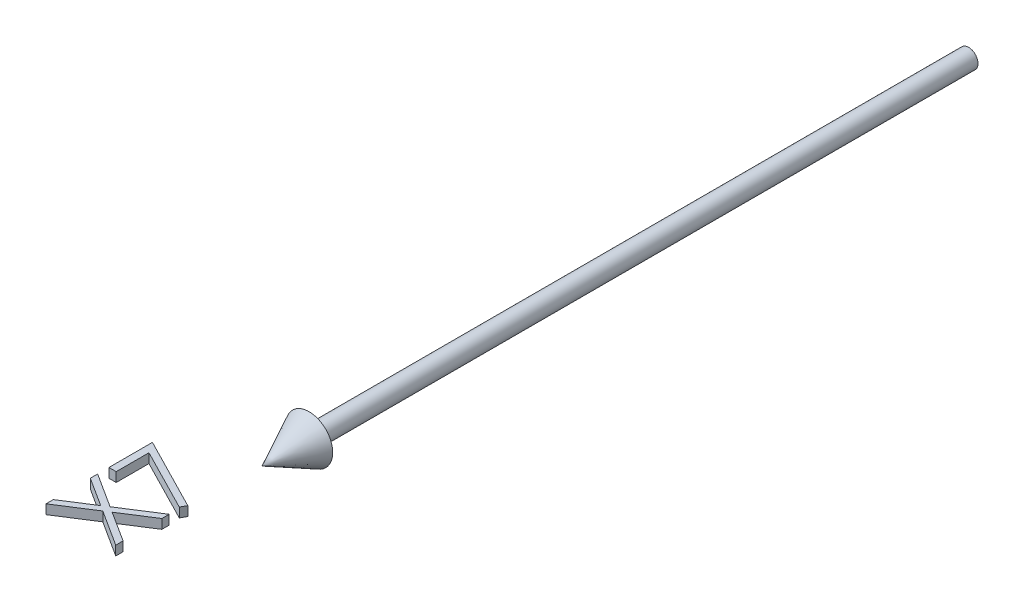
SolidWorks part; units mm, degrees
ref_plane "Front Plane" through (0, 0, 0) normal (0, 0, 1) x (1, 0, 0)
ref_plane "Top Plane" through (0, 0, 0) normal (0, 1, 0) x (1, 0, 0)
ref_plane "Right Plane" through (0, 0, 0) normal (1, 0, 0) x (0, 0, -1)
sketch "Sketch2" plane through (0, 0, 0) normal (0, 1, 0) x (1, 0, 0)
  line L0 (0, 41.95) -> (0, -114.4521) construction
  line L1 (-36.8894, 0) -> (41.4965, 0) construction
  line L2 (0, -150) -> (5, -140)
  line L3 (5, -140) -> (2, -140)
  line L4 (2, -140) -> (2, 0)
  line L5 (2, 0) -> (0, 0)
  line L6 (0, 0) -> (0, -150)
  dimension "D1" = 150
  dimension "D2" = 2
  dimension "D3" = 10
  dimension "D4" = 5
revolve "Revolve1" add sketch "Sketch2" angle 360 about L0
sketch "Sketch3" plane through (0, 0, 0) normal (0, 1, 0) x (1, 0, 0)
  line L0 (0, -157.5) -> (0, -293.8052) construction
  line L2 (-18.6107, 0) -> (20.4361, 0) construction
  text T0 "X7\r\n\r\n\r\n" font "Century Gothic" height 15
  point P8 (0, -168.8691)
  point P9 (0, -200.3685)
  point P10 (0, -293.8052)
  point P11 (0, -165.7633)
  dimension "D1" = 157.5
extrude "Boss-Extrude1" add sketch "Sketch3" against normal blind 1 and the other way blind 1 separate body
equation "\"D1@Sketch2\"=\"frame_arrow_length\""
equation "\"D2@Sketch2\"=\"frame_arrow_odA\"/2"
equation "\"D4@Sketch2\"=\"frame_arrow_head_od\""
equation "\"D3@Sketch2\"=\"frame_arrow_head_length\""
equation "\"frame_arrow_length\"=150"
equation "\"frame_arrow_head_length\"=10"
equation "\"frame_arrow_head_od\"=5"
equation "\"frame_arrow_odA\"=4"
equation "\"D1@Sketch3\"=\"frame_arrow_length\"*1.05"
